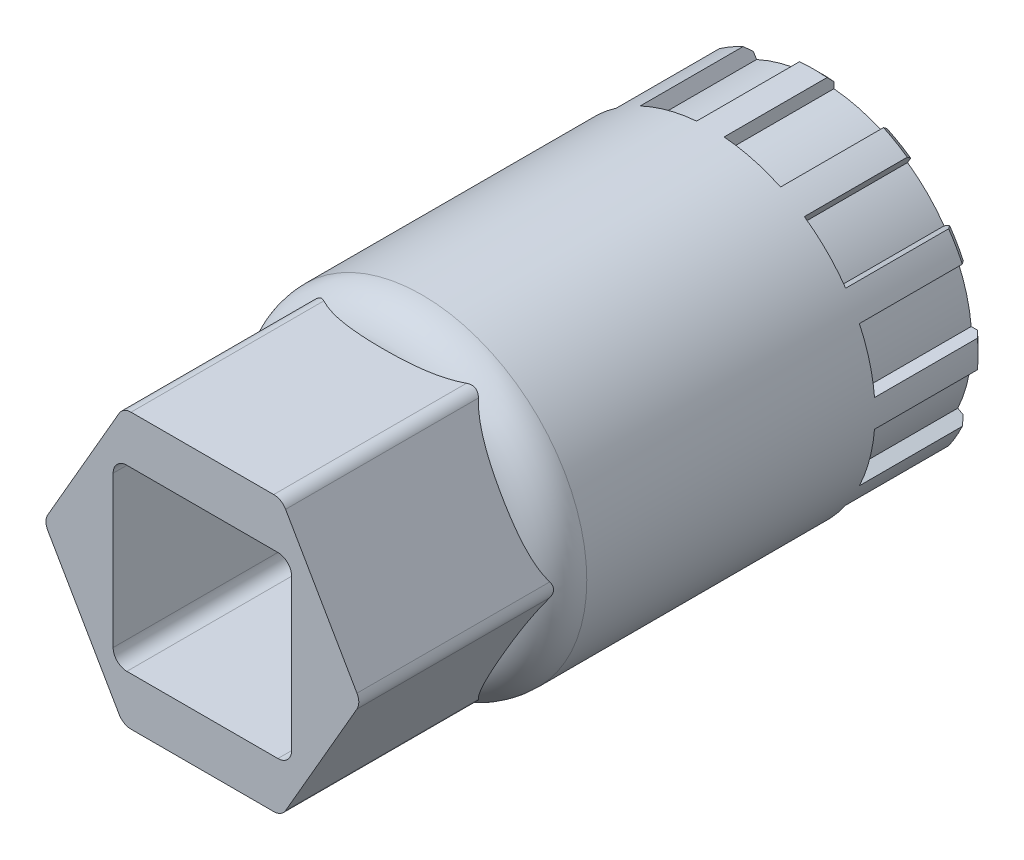
SolidWorks part; units mm, degrees
ref_plane "Спереди" through (0, 0, 0) normal (0, 0, 1) x (1, 0, 0)
ref_plane "Сверху" through (0, 0, 0) normal (0, 1, 0) x (1, 0, 0)
ref_plane "Справа" through (0, 0, 0) normal (1, 0, 0) x (0, 0, -1)
sketch "Эскиз1" plane through (0, 0, 0) normal (0, 0, 1) x (1, 0, 0)
  circle A0 centre (0, 0) radius 12
  dimension "D1" = 24
extrude "Бобышка-Вытянуть1" add sketch "Эскиз1" along normal blind 45
sketch "Эскиз2" plane through (0, 0, 0) normal (0, 0, -1) x (-1, 0, 0)
  line L1 (5.1131, 10.8562) -> (4.634, 10.0263)
  line L3 (1, 11.9583) -> (1, 11)
  line L5 (-1, 11.9583) -> (-1, 11)
  line L9 (6.8452, 9.8562) -> (6.366, 9.0263)
  line L10 (9.8562, 6.8452) -> (9.0263, 6.366)
  line L12 (10.8562, 5.1131) -> (10.0263, 4.634)
  line L13 (11.9583, 1) -> (11, 1)
  line L15 (11.9583, -1) -> (11, -1)
  line L16 (10.8562, -5.1131) -> (10.0263, -4.634)
  line L18 (9.8562, -6.8452) -> (9.0263, -6.366)
  line L19 (6.8452, -9.8562) -> (6.366, -9.0263)
  line L21 (5.1131, -10.8562) -> (4.634, -10.0263)
  line L22 (1, -11.9583) -> (1, -11)
  line L24 (-1, -11.9583) -> (-1, -11)
  line L25 (-5.1131, -10.8562) -> (-4.634, -10.0263)
  line L27 (-6.8452, -9.8562) -> (-6.366, -9.0263)
  line L28 (-9.8562, -6.8452) -> (-9.0263, -6.366)
  line L30 (-10.8562, -5.1131) -> (-10.0263, -4.634)
  line L31 (-11.9583, -1) -> (-11, -1)
  line L33 (-11.9583, 1) -> (-11, 1)
  line L34 (-10.8562, 5.1131) -> (-10.0263, 4.634)
  line L36 (-9.8562, 6.8452) -> (-9.0263, 6.366)
  line L37 (-6.8452, 9.8562) -> (-6.366, 9.0263)
  line L39 (-5.1131, 10.8562) -> (-4.634, 10.0263)
  line L43 (0, -11) -> (0, -11.0454) construction
  arc A1 (-11.9583, -1) -> (-10.8562, -5.1131) centre (0, 0) ccw
  arc A2 (-11, -1) -> (-10.0263, -4.634) centre (0, 0) ccw
  arc A3 (-10.8562, 5.1131) -> (-11.9583, 1) centre (0, 0) ccw
  arc A4 (-10.0263, 4.634) -> (-11, 1) centre (0, 0) ccw
  arc A5 (-6.366, 9.0263) -> (-9.0263, 6.366) centre (0, 0) ccw
  arc A6 (-6.8452, 9.8562) -> (-9.8562, 6.8452) centre (0, 0) ccw
  arc A7 (-1, 11.9583) -> (-5.1131, 10.8562) centre (0, 0) ccw
  arc A8 (-1, 11) -> (-4.634, 10.0263) centre (0, 0) ccw
  arc A9 (5.1131, 10.8562) -> (1, 11.9583) centre (0, 0) ccw
  arc A10 (4.634, 10.0263) -> (1, 11) centre (0, 0) ccw
  arc A11 (9.0263, 6.366) -> (6.366, 9.0263) centre (0, 0) ccw
  arc A12 (9.8562, 6.8452) -> (6.8452, 9.8562) centre (0, 0) ccw
  arc A13 (11.9583, 1) -> (10.8562, 5.1131) centre (0, 0) ccw
  arc A14 (11, 1) -> (10.0263, 4.634) centre (0, 0) ccw
  arc A15 (10.0263, -4.634) -> (11, -1) centre (0, 0) ccw
  arc A16 (10.8562, -5.1131) -> (11.9583, -1) centre (0, 0) ccw
  arc A17 (6.8452, -9.8562) -> (9.8562, -6.8452) centre (0, 0) ccw
  arc A18 (6.366, -9.0263) -> (9.0263, -6.366) centre (0, 0) ccw
  arc A19 (1, -11) -> (4.634, -10.0263) centre (0, 0) ccw
  arc A20 (1, -11.9583) -> (5.1131, -10.8562) centre (0, 0) ccw
  arc A21 (-5.1131, -10.8562) -> (-1, -11.9583) centre (0, 0) ccw
  arc A22 (-4.634, -10.0263) -> (-1, -11) centre (0, 0) ccw
  arc A23 (-9.0263, -6.366) -> (-6.366, -9.0263) centre (0, 0) ccw
  arc A24 (-9.8562, -6.8452) -> (-6.8452, -9.8562) centre (0, 0) ccw
  point P59 (0, 0)
  dimension "D1" = 12
  dimension "D2" = 2
extrude "Вырез-Вытянуть1" cut sketch "Эскиз2" against normal blind 8
sketch "Эскиз3" plane through (0, 0, 0) normal (0, 0, -1) x (-1, 0, 0)
  circle A0 centre (0, 0) radius 10.25
  dimension "D1" = 20.5
extrude "Вырез-Вытянуть2" cut sketch "Эскиз3" against normal blind 17
sketch "Эскиз4" plane through (0, 0, 45) normal (0, 0, 1) x (1, 0, 0)
  line L1 (-11.547, 0) -> (-5.7735, -10)
  line L2 (-5.7735, -10) -> (5.7735, -10)
  line L3 (5.7735, -10) -> (11.547, 0)
  line L4 (11.547, 0) -> (5.7735, 10)
  line L5 (5.7735, 10) -> (-5.7735, 10)
  line L6 (-5.7735, 10) -> (-11.547, 0)
  circle A0 centre (0, 0) radius 10 construction
  circle A1 centre (0, 0) radius 12
  dimension "D1" = 20
extrude "Вырез-Вытянуть3" cut sketch "Эскиз4" against normal blind 13
fillet "Скругление1" radius 1 6 edges at (5.7735, 10, 38.5) (11.547, 0, 38.5) (5.7735, -10, 38.5) (-5.7735, -10, 38.5) (-11.547, 0, 38.5) (-5.7735, 10, 38.5)
sketch "Эскиз5" plane through (0, 0, 45) normal (0, 0, 1) x (1, 0, 0)
  line L1 (6.5, 6.5) -> (-6.5, 6.5)
  line L2 (6.5, 6.5) -> (6.5, -6.5)
  line L3 (6.5, -6.5) -> (-6.5, -6.5)
  line L4 (-6.5, 6.5) -> (-6.5, -6.5)
  line L5 (6.5, 6.5) -> (-6.5, -6.5) construction
  line L6 (6.5, -6.5) -> (-6.5, 6.5) construction
  point P0 (0, 0)
  dimension "D1" = 13
  dimension "D2" = 13
extrude "Вырез-Вытянуть4" cut sketch "Эскиз5" against normal blind 19
sketch "Эскиз6" plane through (0, 0, 26) normal (0, 0, 1) x (1, 0, 0)
  circle A0 centre (0, 0) radius 5
  dimension "D1" = 10
extrude "Вырез-Вытянуть5" cut sketch "Эскиз6" against normal blind 19
chamfer "Фаска1" distance 0.5 angle 45 12 edges at (-10.3923, 6, 0) (-12, 0, 0) (-10.3923, -6, 0) (-6, -10.3923, 0) (0, -12, 0) (6, -10.3923, 0) (10.3923, -6, 0) (12, 0, 0) (10.3923, 6, 0) (6, 10.3923, 0) (0, 12, 0) (-6, 10.3923, 0)
fillet "Скругление4" radius 1 1 edges at (5, 0, 26)
fillet "Скругление5" radius 1 2 edges at (-5, 0, 17) (-10.25, 0, 17)
fillet "Скругление6" radius 3 1 edges at (12, 0, 32)
fillet "Скругление7" radius 1 4 edges at (-6.5, -6.5, 35.5) (-6.5, 6.5, 35.5) (6.5, 6.5, 35.5) (6.5, -6.5, 35.5)
